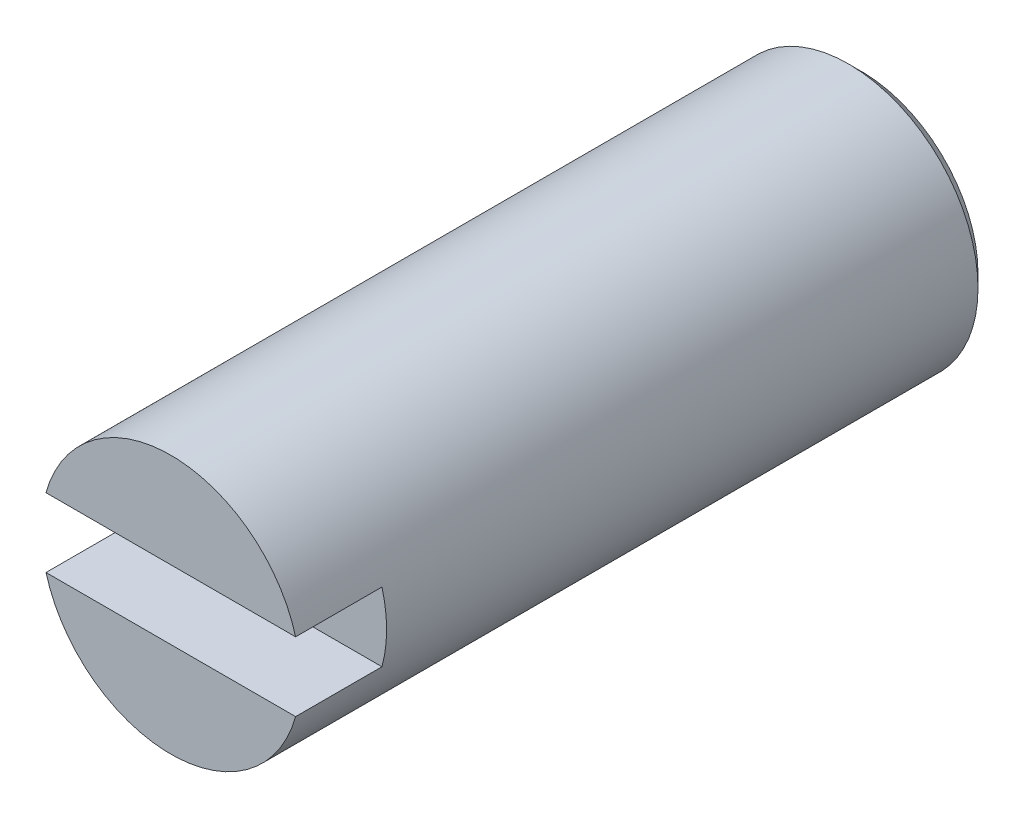
SolidWorks part; units mm, degrees
material "AISI 304"
ref_plane "Front Plane" through (0, 0, 0) normal (0, 0, 1) x (1, 0, 0)
ref_plane "Top Plane" through (0, 0, 0) normal (0, 1, 0) x (1, 0, 0)
ref_plane "Right Plane" through (0, 0, 0) normal (1, 0, 0) x (0, 0, -1)
sketch "Sketch1" plane through (0, 0, 0) normal (0, 0, 1) x (1, 0, 0)
  circle A0 centre (0, 0) radius 1.5
  dimension "D1" = 3
extrude "Boss-Extrude1" add sketch "Sketch1" along normal mid plane 8 contours A0
cosmetic thread "Cosmetic Thread1" parameters "D2"=2.439
chamfer "Chamfer1" distance 0.15 angle 45 1 edges at (1.5, 0, -4)
sketch "Sketch3" plane through (0, 0, 4) normal (0, 0, 1) x (1, 0, 0)
  line L0 (1.65, 0) -> (-1.65, 0) construction
  line L1 (1.5, -0.4) -> (-1.5, -0.4)
  line L2 (1.5, -0.4) -> (1.5, 0.4)
  line L3 (1.5, 0.4) -> (-1.5, 0.4)
  line L4 (-1.5, -0.4) -> (-1.5, 0.4)
  line L5 (1.5, -0.4) -> (-1.5, 0.4) construction
  line L6 (1.5, 0.4) -> (-1.5, -0.4) construction
  circle A0 centre (0, 0) radius 1.5 construction
  point P0 (0, 0)
  point P7 (0, 0)
  dimension "D1" = 0.8
extrude "Cut-Extrude1" cut sketch "Sketch3" against normal blind 1 contours L3 L4 L1 L2
